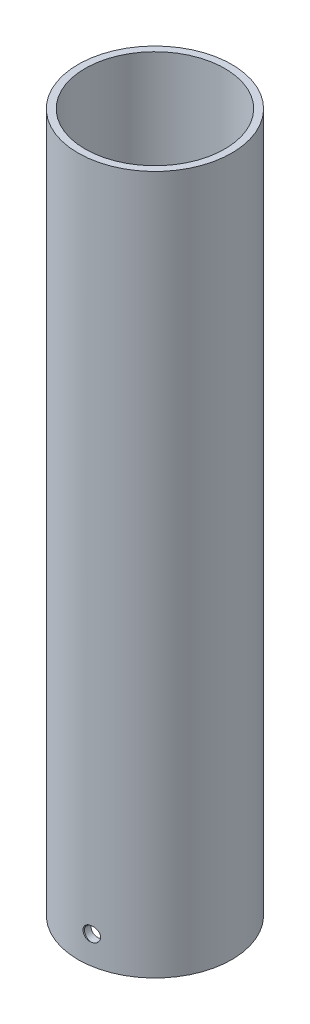
SolidWorks part; units mm, degrees
ref_plane "Front Plane" through (0, 0, 0) normal (0, 0, 1) x (1, 0, 0)
ref_plane "Top Plane" through (0, 0, 0) normal (0, 1, 0) x (1, 0, 0)
ref_plane "Right Plane" through (0, 0, 0) normal (1, 0, 0) x (0, 0, -1)
sketch "Sketch1" plane through (0, 0, 0) normal (0, 1, 0) x (1, 0, 0)
  circle A0 centre (0, 0) radius 50
  circle A1 centre (0, 0) radius 55
  dimension "D1" = 5
  dimension "D2" = 100
extrude "Boss-Extrude2" add sketch "Sketch1" against normal blind 500
ref_plane "Drain hole level" through (0, -480, 0) normal (0, 1, 0) x (1, 0, 0)
ref_plane "Parallel to Mantle" through (0, 0, 55) normal (0, 0, 1) x (1, 0, 0)
hole_wizard "1/8 NPT Tapped Hole1" positions "Sketch4" profile "Sketch6" size "1/8" standard "ANSI Inch"
sketch "Sketch4" plane through (0, 0, 55) normal (0, 0, 1) x (1, 0, 0)
  point P0 (9.082, -479.986)
  point P4 (0, 0)
  point P5 (10.4448, -480.6228)
  point P6 (9.082, -479.986)
sketch "Sketch6" plane through (9.082, -479.986, 55) normal (1, 0, 0) x (0, -1, 0)
  line L0 (0, 0) -> (0, 14.1535)
  line L1 (4.2164, 11.62) -> (0, 14.1535)
  line L2 (-4.2164, 11.62) -> (0, 14.1535) construction
  line L3 (4.2164, 11.62) -> (4.2164, 6.92)
  line L4 (4.2164, 6.92) -> (4.9552, 6.92)
  line L5 (4.9552, 6.92) -> (5.1434, 0.635)
  line L6 (5.1434, 0.635) -> (5.7784, 0)
  line L7 (5.7784, 0) -> (0, 0)
  line L8 (0, -6.35) -> (0, 107.95) construction
  line L9 (-5.1434, 0.635) -> (-5.7784, 0) construction
  line L11 (-4.2164, 6.92) -> (-4.9552, 6.92) construction
  line L12 (-4.9552, 6.92) -> (-5.1434, 0.635) construction
  dimension "Tap Drill Dia." = 8.4328
  dimension "Tap Drill Depth" = 11.62
  dimension "Thread Dia." = 10.2867
  dimension "Thread Angle" = 3.43
  dimension "Thread Depth" = 6.92
  dimension "C'Sink Dia." = 11.5567
  dimension "C'Sink Angle" = 90
  dimension "Drill Angle" = 118
